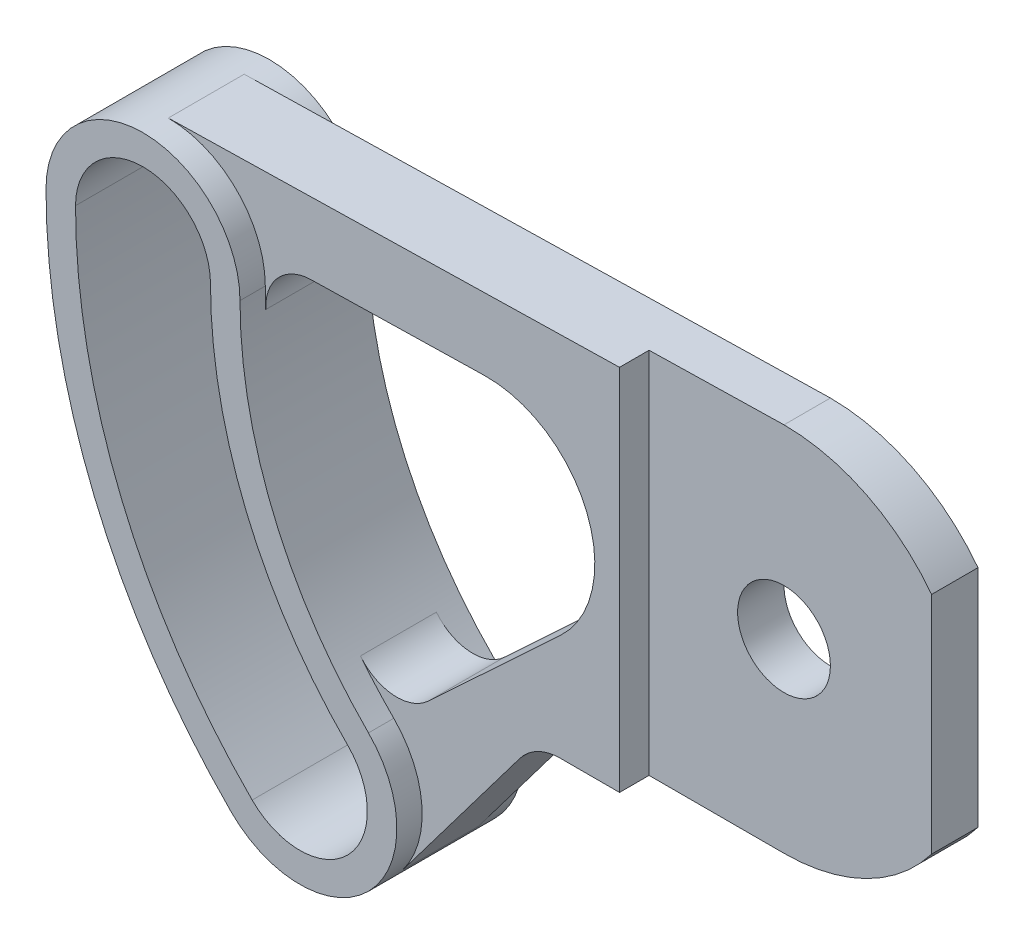
SolidWorks part; units mm, degrees
ref_plane "Front Plane" through (0, 0, 0) normal (0, 0, 1) x (1, 0, 0)
ref_plane "Top Plane" through (0, 0, 0) normal (0, 1, 0) x (1, 0, 0)
ref_plane "Right Plane" through (0, 0, 0) normal (1, 0, 0) x (0, 0, -1)
sketch "Sketch1" plane through (0, 0, 0) normal (0, 0, 1) x (1, 0, 0)
  line L0 (35, -26.6646) -> (35, 26.6646)
  line L1 (0, 0) -> (-193.0195, 0) construction
  line L2 (-12, 18) -> (-193.0195, 18) construction
  line L3 (-12, 18) -> (-165.0496, -135.0496) construction
  line L4 (-139, 41) -> (0, 44)
  line L5 (0, -44) -> (-46.0231, -44)
  line L6 (-55.6009, -48.7705) -> (-83.4451, -85.6591)
  line L7 (-116.9295, 24.4724) -> (-64.0329, 25.6141)
  line L8 (-32, 43.3094) -> (-32, -44)
  line L9 (-46.0231, -18.752) -> (-85.5391, -55.5391)
  circle A0 centre (0, 0) radius 11
  arc A1 (0, -44) -> (35, 26.6646) centre (0, 0) ccw
  arc A2 (-101.8026, -71.8026) -> (-139, 18) centre (-12, 18) cw construction
  arc A3 (-162, 18) -> (-118.066, -88.066) centre (-12, 18) ccw
  arc A4 (-116, 18) -> (-85.5391, -55.5391) centre (-12, 18) ccw
  arc A5 (-116, 18) -> (-162, 18) centre (-139, 18) ccw
  arc A6 (-118.066, -88.066) -> (-85.5391, -55.5391) centre (-101.8026, -71.8026) ccw
  arc A8 (-46.0231, -44) -> (-55.6009, -48.7705) centre (-46.0231, -56) ccw
  arc A9 (-155, 18) -> (-113.1163, -83.1163) centre (-12, 18) ccw
  arc A10 (-113.1163, -83.1163) -> (-90.4889, -60.4889) centre (-101.8026, -71.8026) ccw
  arc A11 (-123, 18) -> (-90.4889, -60.4889) centre (-12, 18) ccw
  arc A12 (-123, 18) -> (-155, 18) centre (-139, 18) ccw
  circle A13 centre (-63.4801, 0) radius 25.62
  arc A14 (0, -44) -> (-32, 30.1993) centre (0, 0) ccw
  arc A15 (-40.1497, 18) -> (-41.8189, 13.6814) centre (0, 0) ccw
  point P4 (-12, 18)
  point P14 (-129.3327, -30.6008)
  point P20 (0, 0)
  point P25 (0, 0)
  point P34 (-52, -44)
  point P38 (-46.0231, -44)
  point P46 (0, 0)
  point P48 (-64.6247, 0)
  point P49 (0, 0)
  point P50 (-65.9981, 0)
  point P51 (0, 0)
  dimension "D1" = 22
  dimension "D2" = 88
  dimension "D7" = 23
  dimension "D8" = 127
  dimension "D11" = 67
  dimension "D12" = 12
  dimension "D3" = 12
  dimension "D4" = 18
  dimension "D5" = 35
  dimension "D6" = 45
  dimension "D9" = 52
  dimension "D10" = 17
  dimension "D13" = 7
extrude "Boss-Extrude1" add sketch "Sketch1" along normal mid plane 30 contours A3 A6 A4 A5 A12 A11 A10 A9 region at (-126.1681, 35.1353, 0)
extrude "Boss-Extrude2" add sketch "Sketch1<3>" along normal mid plane 18 contours A13 L9 A6 L6 A8 L5 L8 L4 A5 L7 | L0 A14 L4 L8 L5 A1 A0 | A14 L4 L8 region at (19.038, -38.4376, 0) region at (-39.0115, -42.3242, 0) region at (-24.5291, 39.6697, 0)
sketch "Sketch1<3>" plane through (0, 0, 0) normal (0, 0, 1) x (1, 0, 0) same geometry as "Sketch1"
extrude "Cut-Extrude1" cut sketch "Sketch1<5>" against normal blind 7 from surface contours A14 L4 L8 | L0 A14 L4 L8 L5 A1 A0 region at (19.038, -38.4376, 0) region at (-24.5291, 39.6697, 0) starting at face at (-44.9521, -12.5197, 9)
sketch "Sketch1<5>" plane through (0, 0, 0) normal (0, 0, 1) x (1, 0, 0) same geometry as "Sketch1"
fillet "Fillet1" radius 11 2 edges at (-116.9295, 24.4724, 0) (-85.5391, -55.5391, 0)
